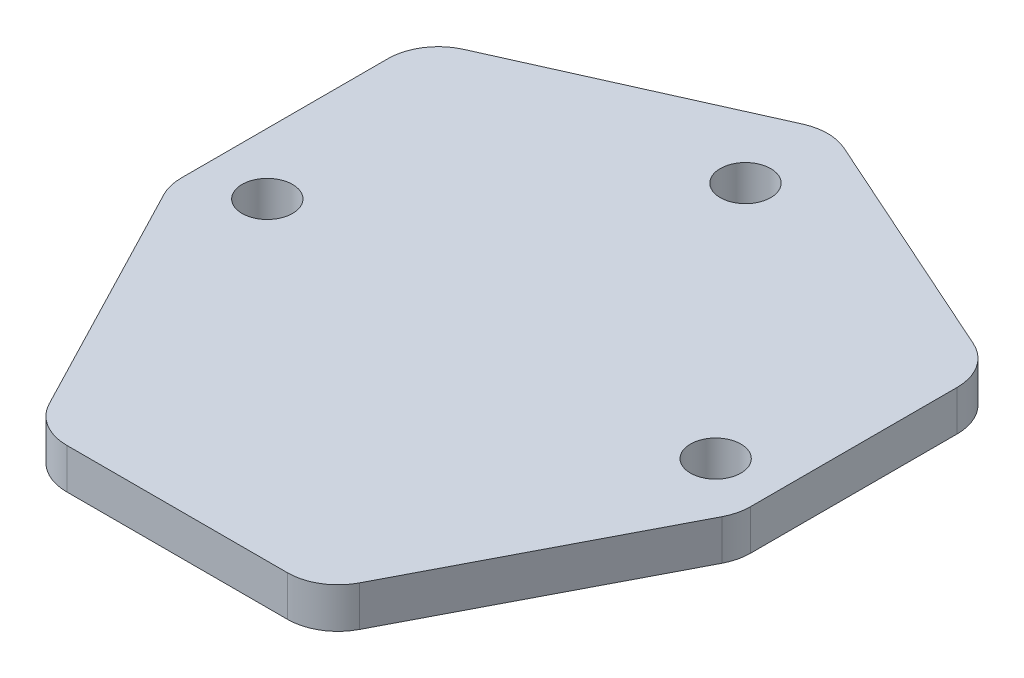
SolidWorks part; units mm, degrees
material "6061 Alloy"
ref_plane "Front Plane" through (0, 0, 0) normal (0, 0, 1) x (1, 0, 0)
ref_plane "Top Plane" through (0, 0, 0) normal (0, 1, 0) x (1, 0, 0)
ref_plane "Right Plane" through (0, 0, 0) normal (1, 0, 0) x (0, 0, -1)
sketch "Sketch1" plane through (0, 0, 0) normal (0, 1, 0) x (1, 0, 0)
  line L0 (1.5627, 4.5778) -> (1.5627, -20.3405)
  line L1 (1.5627, -20.3405) -> (15.7987, -47.7519)
  line L2 (15.7987, -47.7519) -> (29.7703, -47.7519)
  line L3 (29.7703, -47.7519) -> (29.7703, 17.1115) construction
  line L4 (29.7703, 17.196) -> (1.5627, 4.5778)
  line L5 (43.742, -47.7519) -> (29.7703, -47.7519)
  line L6 (57.9779, -20.3405) -> (43.742, -47.7519)
  line L7 (57.9779, 4.5778) -> (57.9779, -20.3405)
  line L8 (29.7703, 17.196) -> (57.9779, 4.5778)
  circle A1 centre (52.1231, -16.7368) radius 2.5
  circle A2 centre (29.9593, 8.3822) radius 2.5
  circle A3 centre (7.6245, -16.6689) radius 2.5
  dimension "D1" = 5
  dimension "D2" = 5
extrude "Boss-Extrude2" add sketch "Sketch1" along normal blind 4
fillet "Fillet1" radius 5 7 edges at (15.7987, 2, 47.7519) (43.742, 2, 47.7519) (57.9779, 2, 20.3405) (57.9779, 2, -4.5778) (1.5627, 2, -4.5778) (29.7703, 2, -17.196) (1.5627, 2, 20.3405)
